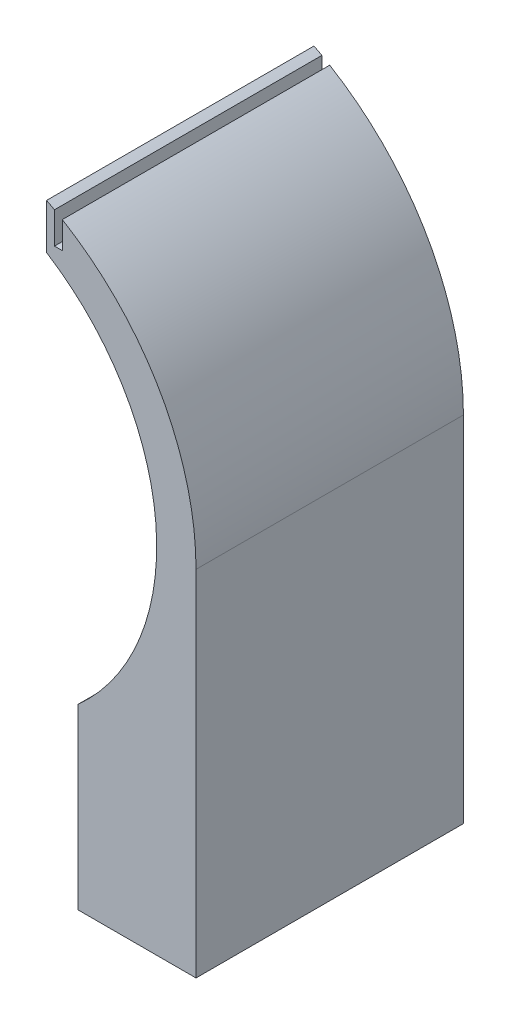
SolidWorks part; units mm, degrees
material "201 Annealed Stainless Steel (SS)"
ref_plane "Front Plane" through (0, 0, 0) normal (0, 0, 1) x (1, 0, 0)
ref_plane "Top Plane" through (0, 0, 0) normal (0, 1, 0) x (1, 0, 0)
ref_plane "Right Plane" through (0, 0, 0) normal (1, 0, 0) x (0, 0, -1)
sketch "Sketch2" plane through (0, 0, 0) normal (0, 0, 1) x (1, 0, 0)
  line L0 (-81.7487, 0) -> (129.7647, 0) construction
  line L1 (0, 82.2046) -> (0, -175) construction
  line L2 (80, 0) -> (80, 108.9269) construction
  line L3 (100, -111.8034) -> (100, -225)
  line L5 (175, 0) -> (175, -225)
  line L6 (175, -225) -> (100, -225)
  line L7 (80, 155.6438) -> (80, 126.8858)
  line L8 (0, -175) -> (0, -225) construction
  line L9 (0, -225) -> (111.0903, -225) construction
  line L10 (-100, -111.8034) -> (100, -111.8034) construction
  line L11 (85, 152.9706) -> (85, 132.9706)
  line L12 (85, 132.9706) -> (90, 132.9706)
  line L13 (90, 132.9706) -> (90, 150.0833)
  circle A0 centre (0, 0) radius 150 construction
  circle A1 centre (0, 0) radius 175 construction
  arc A2 (80, 126.8858) -> (100, -111.8034) centre (0, 0) cw
  arc A3 (175, 0) -> (90, 150.0833) centre (0, 0) ccw
  arc A4 (85, 152.9706) -> (80, 155.6438) centre (0, 0) ccw
  dimension "D1" = 300
  dimension "D2" = 350
  dimension "D5" = 50
  dimension "D3" = 90
  dimension "D4" = 20
  dimension "D6" = 200
  dimension "D7" = 5
  dimension "D8" = 5
extrude "Inner Ring - Right Side" add sketch "Sketch2" along normal blind 170
